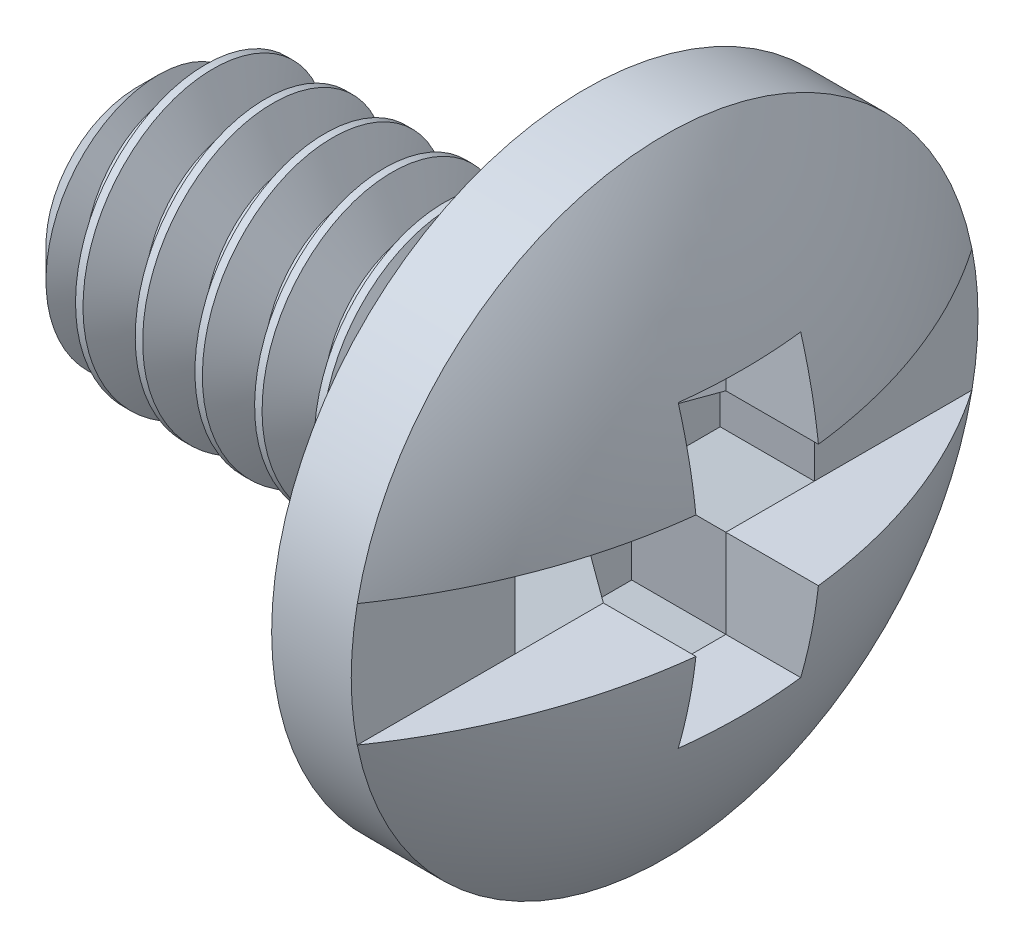
SolidWorks part; units mm, degrees
note: '?' marks a value the reader was unsure of.
ref_plane "Front Plane" through (0, 0, 0) normal (0, 0, 1) x (1, 0, 0)
ref_plane "Top Plane" through (0, 0, 0) normal (0, 1, 0) x (1, 0, 0)
ref_plane "Right Plane" through (0, 0, 0) normal (1, 0, 0) x (0, 0, -1)
sketch "Sketch1" plane through (0, 0, 0) normal (0, 0, 1) x (1, 0, 0)
  line L0 (0, 0) -> (7.9375, 0) construction
  line L1 (0, 2.413) -> (0, -2.413) construction
  line L2 (7.9375, 5.5562) -> (7.9375, -5.5562) construction
  line L3 (7.9375, 0) -> (11.1125, 0) construction
  line L4 (-6.35, 3.175) -> (-6.35, -3.175) construction
  line L5 (-6.35, 0) -> (-44.45, 0) construction
  line L6 (-44.45, 5.5563) -> (-44.45, -5.5563) construction
  line L7 (-6.35, 2.413) -> (-15.875, 2.413) construction
  line L8 (-15.875, 2.413) -> (-15.875, -2.413) construction
  line L9 (-15.875, -2.413) -> (-6.35, -2.413) construction
  line L10 (-44.45, 0) -> (-47.625, 0) construction
  line L11 (7.9375, -5.5562) -> (-44.45, -5.5563) construction
  point P18 (-15.875, 0)
  point P19 (-18.2563, -5.5563)
  point P21 (2.6458, -2.413)
  dimension "Screw Dia" = 4.826
  dimension "Screw Length" = 7.9375
  dimension "Head Dia" = 11.1125
  dimension "Head Height" = 3.175
  dimension "D1" = 6.35
  dimension "Barrel Dia" = 6.35
  dimension "Thread Depth" = 9.525
  dimension "Barrel Length" = 38.1
  dimension "D2" = 2.6458
ref_plane "Plane1" through (11.1125, 0, 0) normal (1, 0, 0) x (0, 0, -1)
sketch "Sketch2" plane through (0, 0, 0) normal (1, 0, 0) x (0, 0, -1)
  circle A0 centre (0, 0) radius 2.413
extrude "Boss-Extrude1" add sketch "Sketch2" along normal up to vertex (7.9375 mm away) up to point (7.9375, 0, 0)
sketch "Sketch4" plane through (0, 0, 0) normal (-1, 0, 0) x (0, 0, 1)
  circle A1 centre (0, 0) radius 2.413
  circle A2 centre (0, 0) radius 2.413
  dimension "D1" = 0
curve "Helix/Spiral1" pitch 1.0583 height 8.9958 turns 8.5 parameters "Pitch"=1.0583
chamfer "Chamfer1" distance 0.7937 angle 45 1 edges at (0, 0, -2.413)
sketch "Sketch6" plane through (0, 0, 0) normal (0, 0, 1) x (1, 0, 0)
  line L0 (7.9375, 0) -> (7.9375, 5.5562)
  line L1 (7.9375, 5.5562) -> (9.3486, 5.5562)
  line L2 (11.1125, 0) -> (11.1125, 5.5563) construction
  line L3 (11.1125, 0) -> (7.9375, 0) construction
  line L5 (7.9375, 0) -> (11.1125, 0)
  line L6 (11.1125, 0) -> (11.1125, -1.9812) construction
  arc A0 (11.1125, 0) -> (9.3486, 5.5562) centre (1.4795, 0) ccw
  point P6 (8.2903, 5.5562)
  point P10 (11.1125, -1.9812)
  dimension "D1" = 1.4111
  dimension "D2" = 1.0583
revolve "Revolve1" add sketch "Sketch6" angle 360 about L3
sketch "Sketch17" plane through (11.1125, 0, 0) normal (1, 0, 0) x (0, 0, -1)
  line L0 (-5.5562, 0) -> (5.5562, 0) construction
  line L1 (-5.5563, 1.0858) -> (5.5563, 1.0858)
  line L2 (-5.5563, 1.0858) -> (-5.5563, -1.0858)
  line L3 (-5.5563, -1.0858) -> (5.5563, -1.0858)
  line L4 (5.5563, 1.0858) -> (5.5563, -1.0858)
  circle A0 centre (0, 0) radius 5.5562 construction
  dimension "D1" = 2.1717
extrude "Cut-Extrude5" cut sketch "Sketch17" against normal up to vertex (1.7639 mm away) up to point (9.3486, 5.5562, 0)
sketch "Sketch18" plane through (9.3486, 0, 0) normal (1, 0, 0) x (0, 0, -1)
  line L0 (0, 0) -> (0, 2.6543) construction
  line L1 (-1.0858, 2.6543) -> (1.0859, 2.6543)
  line L2 (-1.0858, 2.6543) -> (-1.0858, -2.6543)
  line L3 (-1.0858, -2.6543) -> (1.0859, -2.6543)
  line L4 (1.0859, 2.6543) -> (1.0859, -2.6543)
  line L5 (0, 0) -> (1.0859, 0) construction
  dimension "D1" = 2.1717
  dimension "D2" = 5.3086
extrude "Cut-Extrude6" cut sketch "Sketch18" along normal through all and the other way up to vertex (1.0583 mm away) draft 30
sketch "Sketch19" plane through (9.3486, 0, 0) normal (1, 0, 0) x (0, 0, -1)
  line L0 (-2.6543, 0) -> (2.6543, 0) construction
  line L1 (-2.6543, 1.0858) -> (2.6543, 1.0858)
  line L2 (-2.6543, 1.0858) -> (-2.6543, -1.0859)
  line L3 (-2.6543, -1.0859) -> (2.6543, -1.0858)
  line L4 (2.6543, 1.0858) -> (2.6543, -1.0858)
  line L5 (-1.0858, 2.6543) -> (1.0859, 2.6543) construction
  line L6 (-1.0858, 2.6543) -> (-1.0858, -2.6543) construction
extrude "Cut-Extrude7" cut sketch "Sketch19" against normal up to vertex (1.0583 mm away) draft 30 up to point (8.2903, 5.5562, 0)
split "Split1" bodies to split 101 resulting bodies 121
sketch "Sketch5" plane through (0, 0, 0) normal (0, 0, 1) x (1, 0, 0)
  line L0 (0, 2.413) -> (-0.926, 2.413)
  line L1 (0, 2.413) -> (-0.3969, 1.7256)
  line L2 (-0.3969, 1.7256) -> (-0.5292, 1.7256)
  line L3 (-0.5292, 1.7256) -> (-0.926, 2.413)
  line L4 (-0.463, 1.7256) -> (-0.463, 2.413) construction
  line L5 (-0.1984, 2.0693) -> (-0.7276, 2.0693) construction
  dimension "D1" = 0.1323
  dimension "D2" = 0.5292
  dimension "D3" = 60
sweep "Cut-Sweep1" cut profiles "Sketch5" path "Helix/Spiral1"
combine bodies "Combine1" operation type add bodies to combine 120 102
ref_axis "Axis1" through (9.3486, 0, 0) along (-1, 0, 0)?
ref_plane "Plane2" through (7.9375, 0, 0) normal (-1, 0, 0) x (0, 0, 1)
equation "\"D1@Sketch5\" = \"Pitch@Helix/Spiral1\"*.125"
equation "\"D2@Sketch5\" = \"Pitch@Helix/Spiral1\"*.50"
equation "\"D3@Helix/Spiral1\" = \"Screw Length@Sketch1\"+\"Pitch@Helix/Spiral1\""
equation "\"D1@Chamfer1\" = \"Pitch@Helix/Spiral1\"*.750"
equation "\"D1@Sketch6\" = \"Head Height@Sketch1\"/2.250"
equation "\"D2@Sketch1\" = \"Pitch@Helix/Spiral1\"*2.50"
equation "\"D1@Sketch17\" = \"Screw Dia@Sketch1\"*.45"
equation "\"D1@Sketch18\" = \"D1@Sketch17\"*1"
equation "\"D2@Sketch18\" = \"Screw Dia@Sketch1\"*1.1"
equation "\"D2@Sketch6\" = \"D1@Sketch6\"*.750"
